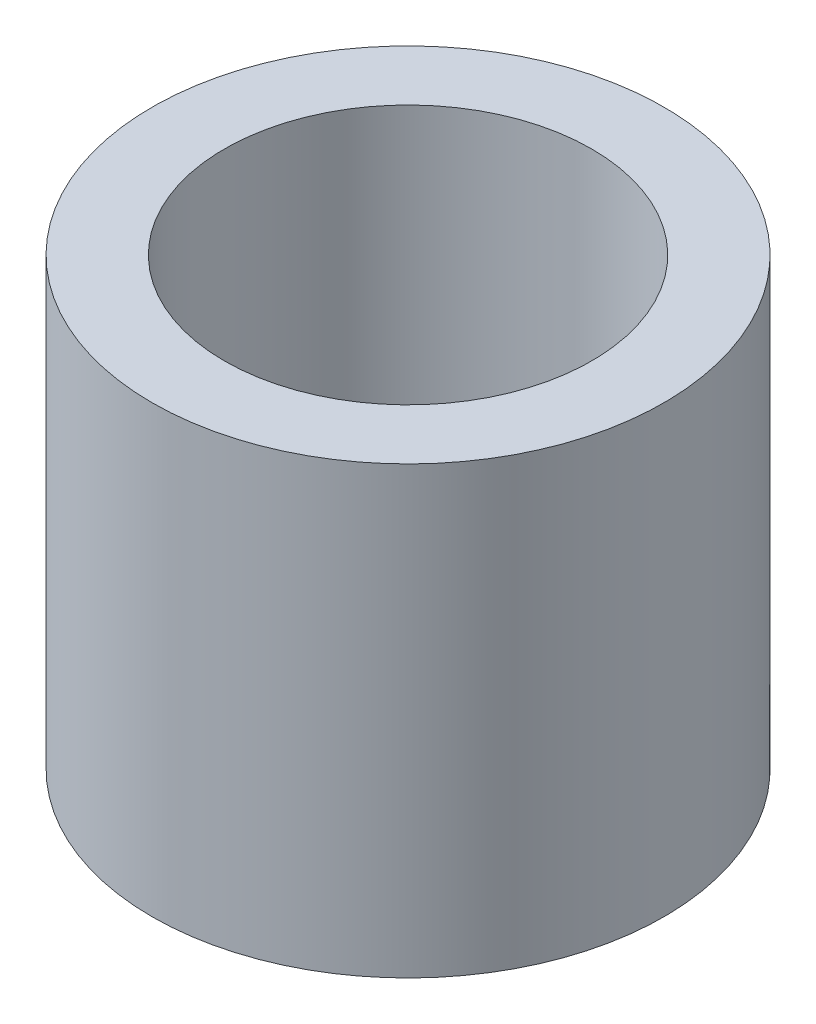
SolidWorks part; units mm, degrees
ref_plane "Спереди" through (0, 0, 0) normal (0, 0, 1) x (1, 0, 0)
ref_plane "Сверху" through (0, 0, 0) normal (0, 1, 0) x (1, 0, 0)
ref_plane "Справа" through (0, 0, 0) normal (1, 0, 0) x (0, 0, -1)
sketch "Эскиз1" plane through (0, 0, 0) normal (0, 1, 0) x (1, 0, 0)
  circle A0 centre (0, 0) radius 23
  dimension "D1" = 46
extrude "Бобышка-Вытянуть1" add sketch "Эскиз1" along normal blind 5
sketch "Эскиз2" plane through (0, 5, 0) normal (0, 1, 0) x (1, 0, 0)
  circle A0 centre (0, 0) radius 23
  circle A1 centre (0, 0) radius 16.5
  circle A2 centre (0, 0) radius 23 construction
  dimension "D1" = 33
  dimension "D2" = 0
extrude "Бобышка-Вытянуть2" add sketch "Эскиз2" along normal blind 35
